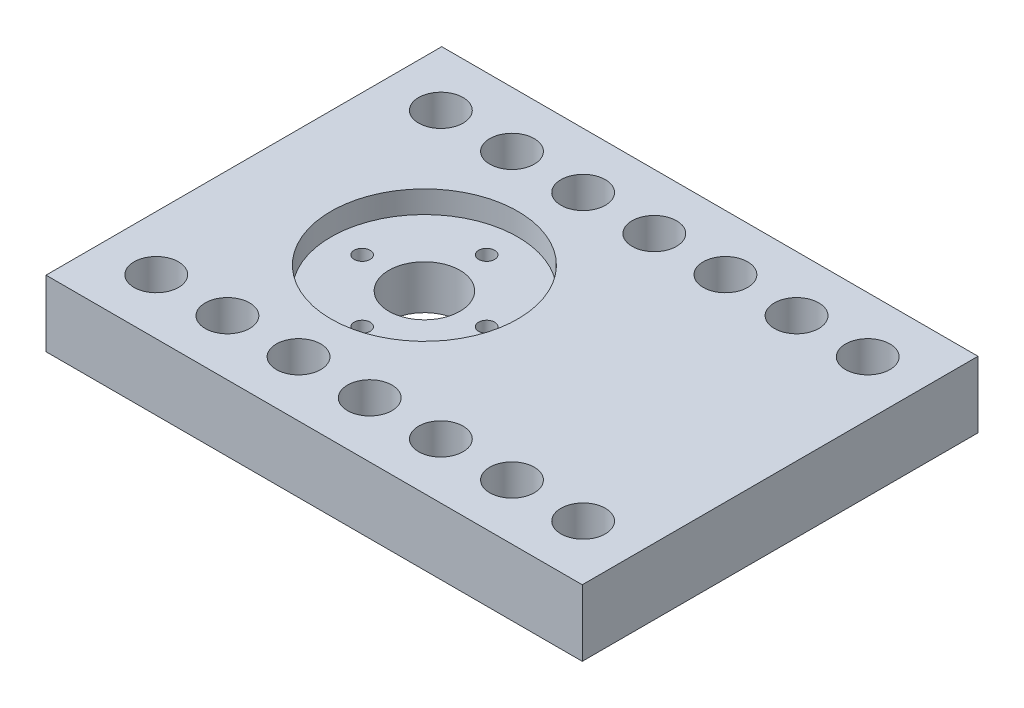
SolidWorks part; units mm, degrees
ref_plane "Front Plane" through (0, 0, 0) normal (0, 0, 1) x (1, 0, 0)
ref_plane "Top Plane" through (0, 0, 0) normal (0, 1, 0) x (1, 0, 0)
ref_plane "Right Plane" through (0, 0, 0) normal (1, 0, 0) x (0, 0, -1)
sketch "Sketch3" plane through (0, 0, 0) normal (0, 1, 0) x (1, 0, 0)
  line L0 (-52.2632, 0) -> (55.5227, 0) construction
  line L1 (0, 43.998) -> (0, -43.557) construction
  line L2 (-9.85, 40.6896) -> (-9.85, -33.1895) construction
  circle A0 centre (-9.85, 0) radius 10 construction
  circle A1 centre (-9.85, 0) radius 7 construction
  circle A2 centre (-9.85, 7) radius 0.9
  circle A3 centre (-16.85, 0) radius 0.9
  circle A4 centre (-9.85, -7) radius 0.9
  circle A5 centre (-2.85, 0) radius 0.9
  circle A6 centre (-9.85, 0) radius 4
  line B0 (-34.3973, 0) -> (32.9918, 0) construction
  line B1 (-20.15, 9.75) -> (-20.15, -9.75) construction
  line B2 (20.15, 9.75) -> (20.15, -9.75) construction
  line B3 (-20.15, 9.75) -> (20.15, -9.75) construction
  line B4 (-20.15, -9.75) -> (20.15, 9.75) construction
  line B5 (0, 26.5192) -> (0, -28.2205) construction
  line B6 (-30.15, 22.25) -> (30.15, 22.25)
  line B7 (-30.15, 22.25) -> (-30.15, -22.25)
  line B8 (-30.15, -22.25) -> (30.15, -22.25)
  line B9 (30.15, 22.25) -> (30.15, -22.25)
  line B10 (-27, 9.75) -> (27, 9.75) construction
  line B11 (-27, 9.75) -> (-27, -9.75) construction
  line B12 (-27, -9.75) -> (27, -9.75) construction
  line B13 (27, 9.75) -> (27, -9.75) construction
  line B14 (-27, 9.75) -> (27, -9.75) construction
  line B15 (-27, -9.75) -> (27, 9.75) construction
  dimension "D8" = 1.8
  dimension "D4" = 20
  dimension "D5" = 14
  dimension "D6" = 1.8
  dimension "D7" = 1.8
  dimension "D9" = 1.8
  dimension "D10" = 8
  dimension "D1" = 0
  dimension "D2" = 0
  dimension "D3" = 9.85
sketch_block_instance "Block3-1"
sketch_block "Block3" parameters "D1"=40.3, "D2"=19.5, "D3"=10, "D4"=10, "D5"=54, "D6"=34.5, "D7"=17.25
extrude "Boss-Extrude1" add sketch "Sketch3" along normal blind 7.46
sketch "Sketch4" plane through (0, 7.46, 0) normal (0, 1, 0) x (1, 0, 0)
  line L0 (0, 22.25) -> (0, -22.25) construction
  line L1 (30.15, 22.25) -> (-30.15, 22.25) construction
  line L2 (-30.15, -22.25) -> (30.15, -22.25) construction
  line L3 (-30.15, 0) -> (30.15, 0) construction
  line L4 (-30.15, 22.25) -> (-30.15, -22.25) construction
  line L5 (30.15, -22.25) -> (30.15, 22.25) construction
  line L6 (-9.85, 7) -> (-9.85, -7) construction
  circle A0 centre (-9.85, 0) radius 10.5
  dimension "D1" = 21
extrude "Cut-Extrude1" cut sketch "Sketch4" against normal blind 2.5
sketch "Sketch5" plane through (0, 7.46, 0) normal (0, 1, 0) x (1, 0, 0)
  line L0 (-30.15, 16) -> (30.15, 16) construction
  line L1 (-30.15, 22.25) -> (-30.15, -22.25) construction
  line L2 (30.15, -22.25) -> (30.15, 22.25) construction
  line L3 (30.15, 22.25) -> (-30.15, 22.25) construction
  line L4 (-30.15, -16) -> (30.15, -16) construction
  line L5 (-30.15, -22.25) -> (30.15, -22.25) construction
  line L6 (0, 22.25) -> (0, -22.25) construction
  line L7 (-30.15, 0) -> (30.15, 0) construction
  circle A0 centre (0, 16) radius 2.5
  circle A1 centre (8, 16) radius 2.5
  circle A2 centre (16, 16) radius 2.5
  circle A3 centre (24, 16) radius 2.5
  circle A4 centre (-24, 16) radius 2.5
  circle A5 centre (-16, 16) radius 2.5
  circle A6 centre (-8, 16) radius 2.5
  circle A7 centre (-8, -16) radius 2.5
  circle A8 centre (-16, -16) radius 2.5
  circle A9 centre (-24, -16) radius 2.5
  circle A10 centre (24, -16) radius 2.5
  circle A11 centre (16, -16) radius 2.5
  circle A12 centre (8, -16) radius 2.5
  circle A13 centre (0, -16) radius 2.5
  dimension "D3" = 5
  dimension "D5" = 8
  dimension "D1" = 6.25
  dimension "D2" = 6.25
  dimension "D4" = 4
extrude "Cut-Extrude2" cut sketch "Sketch5" against normal through all
